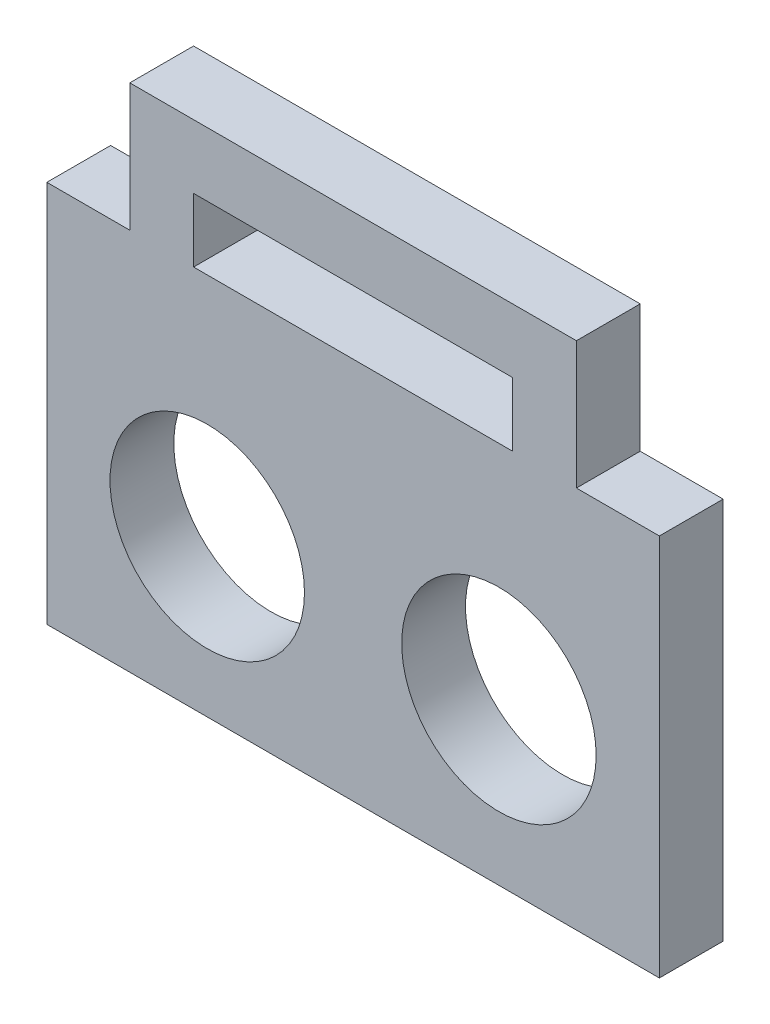
SolidWorks part; units mm, degrees
ref_plane "Přední rovina" through (0, 0, 0) normal (0, 0, 1) x (1, 0, 0)
ref_plane "Horní rovina" through (0, 0, 0) normal (0, 1, 0) x (1, 0, 0)
ref_plane "Pravá rovina" through (0, 0, 0) normal (1, 0, 0) x (0, 0, -1)
sketch "Skica1" plane through (0, 0, 0) normal (0, 0, 1) x (1, 0, 0)
  line L1 (-19.7439, 5.4997) -> (28.2561, 5.4997)
  line L2 (-19.7439, 5.4997) -> (-19.7439, -24.5003)
  line L3 (-19.7439, -24.5003) -> (28.2561, -24.5003)
  line L4 (28.2561, 5.4997) -> (28.2561, -24.5003)
  line L5 (-13.2439, 5.4997) -> (21.7561, 5.4997)
  line L6 (-13.2439, 5.4997) -> (-13.2439, 15.4997)
  line L7 (-13.2439, 15.4997) -> (21.7561, 15.4997)
  line L8 (21.7561, 5.4997) -> (21.7561, 15.4997)
  line L9 (16.7561, 5.4997) -> (-8.2439, 5.4997)
  line L10 (16.7561, 5.4997) -> (16.7561, 10.4997)
  line L11 (16.7561, 10.4997) -> (-8.2439, 10.4997)
  line L12 (-8.2439, 5.4997) -> (-8.2439, 10.4997)
  circle A0 centre (-7.1739, -12.2502) radius 7.62
  circle A1 centre (15.6831, -11.8803) radius 7.62
  dimension "D1" = 22.86
  dimension "D2" = 15.24
  dimension "D3" = 15.24
  dimension "D9" = 12.57
  dimension "D13" = 17.38
  dimension "D4" = 5
  dimension "D5" = 5
  dimension "D6" = 5
  dimension "D7" = 5
  dimension "D8" = 25
  dimension "D10" = 48
  dimension "D11" = 6.5
  dimension "D12" = 30
extrude "Přidat vysunutím1" add sketch "Skica1" along normal blind 5 contours L4 L1 L5 L2 L3 A1 A0 | L1 L12 L11 L10 L8 L7 L6 region at (4.2566, -8.63, 0) region at (4.2561, 11.8886, 0)
